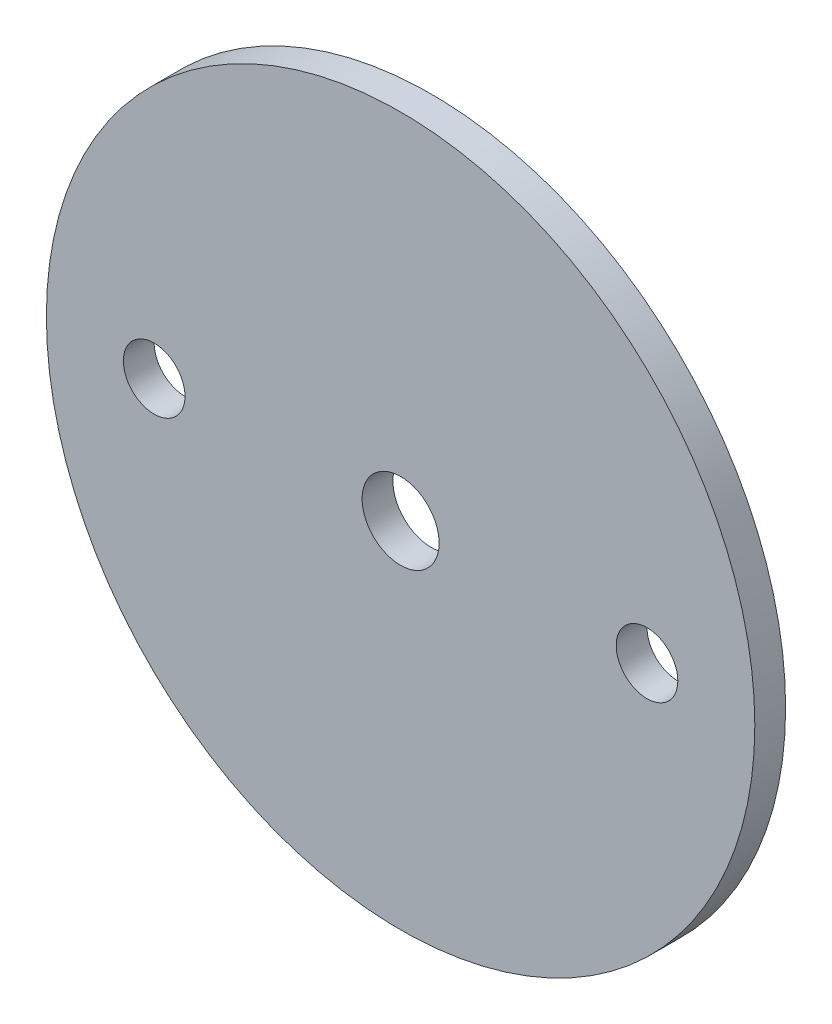
SolidWorks part; units mm, degrees
ref_plane "Front Plane" through (0, 0, 0) normal (0, 0, 1) x (1, 0, 0)
ref_plane "Top Plane" through (0, 0, 0) normal (0, 1, 0) x (1, 0, 0)
ref_plane "Right Plane" through (0, 0, 0) normal (1, 0, 0) x (0, 0, -1)
sketch "Sketch1" plane through (0, 0, 0) normal (0, 0, 1) x (1, 0, 0)
  circle A0 centre (0, 0) radius 36.5125
  dimension "D1" = 73.025
extrude "Boss-Extrude1" add sketch "Sketch1" along normal mid plane 3.175
sketch "Sketch2" plane through (0, 0, 1.5875) normal (0, 0, 1) x (1, 0, 0)
  line L0 (-1000, 0) -> (49000, 0) construction
  line L1 (0, -1000) -> (0, 49000) construction
  point P4 (25.4, 0)
  point P5 (-25.4, 0)
  dimension "D2" = 50.8
  dimension "D1" = 25.4
hole_wizard "1/4 (0.25) Diameter Hole1" positions "Sketch2" profile "Sketch3" hole size "1/4" standard "ANSI Inch" end condition through all
sketch "Sketch3" plane through (-25.4, 0, 1.5875) normal (1, 0, 0) x (0, -1, 0)
  line L0 (0, 0) -> (0, 3.175)
  line L1 (0, 3.175) -> (3.175, 3.175)
  line L2 (3.175, 3.175) -> (3.175, 0)
  line L5 (3.175, 0) -> (0, 0)
  line L11 (0, -6.35) -> (0, 107.95) construction
  dimension "Thru Hole Dia." = 6.35
  dimension "Thru Hole Depth" = 3.175
sketch "Sketch4" plane through (0, 0, 1.5875) normal (0, 0, 1) x (1, 0, 0)
  point P0 (0, 0)
hole_wizard "5/16 (0.3125) Diameter Hole1" positions "Sketch4" profile "Sketch5" hole size "5/16" standard "ANSI Inch"
sketch "Sketch5" plane through (0, 0, 1.5875) normal (1, 0, 0) x (0, -1, 0)
  line L0 (0, 0) -> (0, 3.302)
  line L1 (0, 3.302) -> (3.9687, 3.302)
  line L2 (3.9687, 3.302) -> (3.9688, 0)
  line L5 (3.9688, 0) -> (0, 0)
  line L10 (0, 3.302) -> (-3.9688, 3.302) construction
  line L11 (0, -6.35) -> (0, 107.95) construction
  dimension "Hole Dia." = 7.9375
  dimension "Hole Depth" = 3.302
  dimension "Drill Angle" = 180
equation "\"AIRFRAME_OD\"= 3.142in"
equation "\"AIRFRAME_ID\"= 3.00in"
equation "\"FLAT_T\"= 0.125in"
equation "\"NOSE_EXP_L\"= 3.5in"
equation "\"NOSE_SHOULDER_L\"= 1.5in"
equation "\"MAIN_L\"= 30in"
equation "\"RECO_COUP_L\"= 6in"
equation "\"RECO_SWITCH_L\"= 1.5in"
equation "\"DROGUE_L\"= 14in"
equation "\"ATS_FORE_COUP_L\"= 4in"
equation "\"ATS_AFT_COUP_L\"= 2.5in"
equation "\"LOWER_L\"= 16in"
equation "\"FIN_N\"= 4"
equation "\"CR_AFT_X\"= 0.5in"
equation "\"CR_FORE_X\"= 6in"
equation "\"FIN_ROOT\"= 5in"
equation "\"FIN_X\"= 0.75in"
equation "\"MOTOR_OD\"= 2.25in"
equation "\"MOTOR_ID\"= 2.126in"
equation "\"COUPLER_OD\"= 2.998in"
equation "\"COUPLER_ID\"= 2.875in"
equation "\"D1@Sketch1\"=\"COUPLER_ID\""
equation "\"D1@Boss-Extrude1\"=\"FLAT_T\""
equation "\"RECO_ROD_X\"= 1.5in"
equation "\"ATS_ROD_X\"= 2in"
equation "\"D2@Sketch2\"=\"ATS_ROD_X\""
